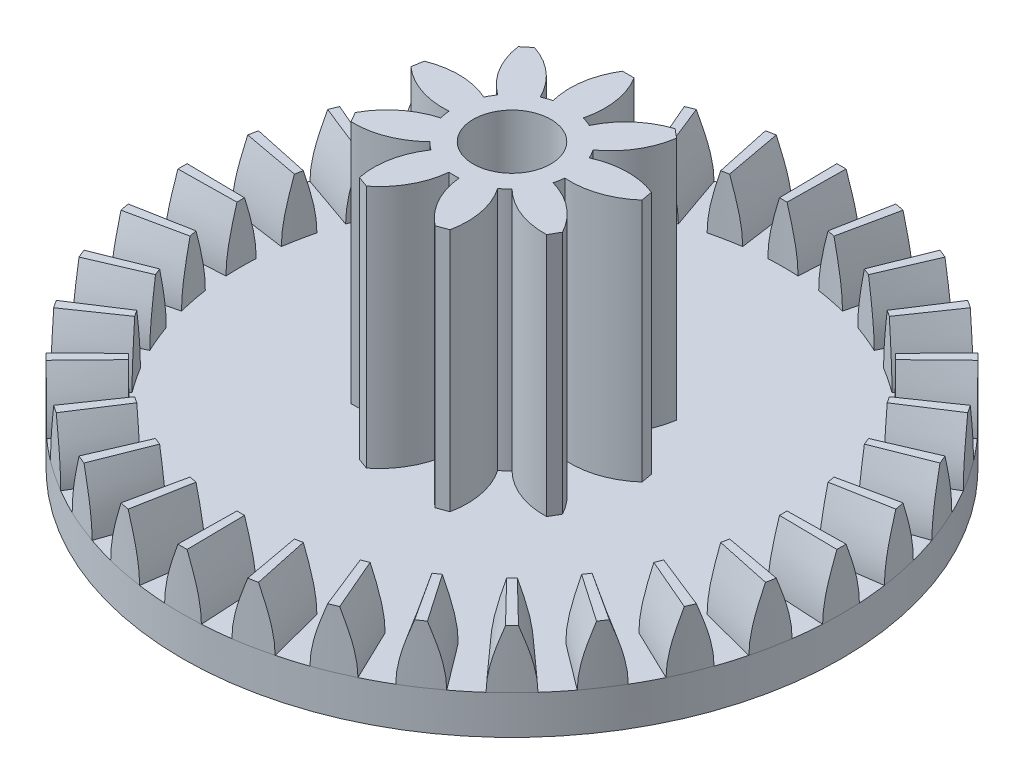
SolidWorks part; units mm, degrees
material "PBT General Purpose"
ref_plane "Front Plane" through (0, 0, 0) normal (0, 0, 1) x (1, 0, 0)
ref_plane "Top Plane" through (0, 0, 0) normal (0, 1, 0) x (1, 0, 0)
ref_plane "Right Plane" through (0, 0, 0) normal (1, 0, 0) x (0, 0, -1)
sketch "Sketch1" plane through (0, 0, 0) normal (0, 1, 0) x (1, 0, 0)
  circle A0 centre (0, 0) radius 8.5
  dimension "D1" = 17
extrude "Boss-Extrude1" add sketch "Sketch1" along normal blind 1
sketch "Sketch3" plane through (0, 1, 0) normal (0, 1, 0) x (1, 0, 0)
  line L0 (0, 0) -> (0, 8.5) construction
  line L1 (0, 0) -> (0.4745, 8.4867) construction
  line L2 (0, 0) -> (-0.4745, 8.4867) construction
  line L3 (-0.3908, 6.9891) -> (-0.4745, 8.4867)
  line L4 (0.3908, 6.9891) -> (0.4745, 8.4867)
  circle A0 centre (0, 0) radius 8.5 construction
  arc A1 (-0.4745, 8.4867) -> (0.4745, 8.4867) centre (0, 0) cw
  arc A2 (-0.3908, 6.9891) -> (0.3908, 6.9891) centre (0, -1.5019) cw
  dimension "D3" = 1.5
  dimension "D1" = 3.2
  dimension "3" = 3.2
ref_plane "Plane1" through (0, 2.5, 0) normal (0, 1, 0) x (1, 0, 0)
sketch "Sketch4" plane through (0, 2.5, 0) normal (0, 1, 0) x (1, 0, 0)
  line L0 (0, 0) -> (0.1187, 8.4992) construction
  line L1 (0, 0) -> (-0.1187, 8.4992) construction
  line L2 (0, 0) -> (0, 8.5) construction
  line L3 (0, 0) -> (0, 8.5) construction
  line L4 (-0.0977, 6.9975) -> (-0.1187, 8.4992)
  line L5 (0.0977, 6.9975) -> (0.1187, 8.4992)
  arc A0 (0.4745, 8.4867) -> (-0.4745, 8.4867) centre (0, 0) ccw construction
  arc A1 (0.1187, 8.4992) -> (-0.1187, 8.4992) centre (0, 0) ccw
  arc A2 (0.3908, 6.9891) -> (-0.3908, 6.9891) centre (0, -1.5019) ccw construction
  arc A3 (0.0977, 6.9975) -> (-0.0977, 6.9975) centre (0, -1.5019) ccw
  dimension "D1" = 0.8
  dimension "D2" = 0.8
loft "Loft1" add profiles "Sketch3", "Sketch4" start constraint normal to profile start tangent length 1 connector at (-0.4745, 1, -8.4867) connector at (-0.1187, 2.5, -8.4992)
pattern_circular "CirPattern1" count 32 over 360 about axis through (0, 1, 0) along (0, 1, 0) of "Loft1"
sketch "Sketch5" plane through (0, 1, 0) normal (0, 1, 0) x (1, 0, 0)
  circle A0 centre (0, 0) radius 1.5
  dimension "D1" = 3
extrude "Boss-Extrude2" add sketch "Sketch5" along normal blind 6.3
sketch "Sketch7" plane through (0, 7.3, 0) normal (0, 1, 0) x (1, 0, 0)
  line L0 (0, 0) -> (0, 3) construction
  line L1 (0, 0) -> (0.7765, 2.8978) construction
  line L2 (0, 0) -> (-0.7765, 2.8978) construction
  line L3 (-0.3882, 1.4489) -> (-0.3825, 1.4277)
  line L4 (0.3882, 1.4489) -> (0.3825, 1.4277)
  line L5 (-0.15, 3) -> (0.15, 3)
  circle A0 centre (0, 0) radius 1.5 construction
  arc A1 (-0.3825, 1.4277) -> (-0.15, 3) centre (1.5493, 1.9453) cw
  arc A2 (0.15, 3) -> (0.3825, 1.4277) centre (-1.5493, 1.9453) cw
  circle A3 centre (0, 0) radius 1.5
  point P12 (0, 3)
  circle M5 centre (0, 0) radius 1.5
  dimension "D2" = 15
  dimension "D5" = 2
  dimension "D1" = 3
  dimension "D3" = 15
  dimension "D4" = 3
  dimension "D6" = 0.3
extrude "Boss-Extrude3" add sketch "Sketch7" against normal up to surface (6.3 mm away) contours A2 L5 A1 L3 L4 M5 region at (0, 7.3, -2.1615) up to face at (0, 1, 1.5)
pattern_circular "CirPattern2" count 9 over 360 about axis through (0, 7.3, 0) along (0, 1, 0) of "Boss-Extrude3"
sketch "Sketch8" plane through (0, 7.3, 0) normal (0, 1, 0) x (1, 0, 0)
  circle A0 centre (0, 0) radius 1
  dimension "D1" = 2
extrude "Cut-Extrude1" cut sketch "Sketch8" against normal through all both and the other way through all
